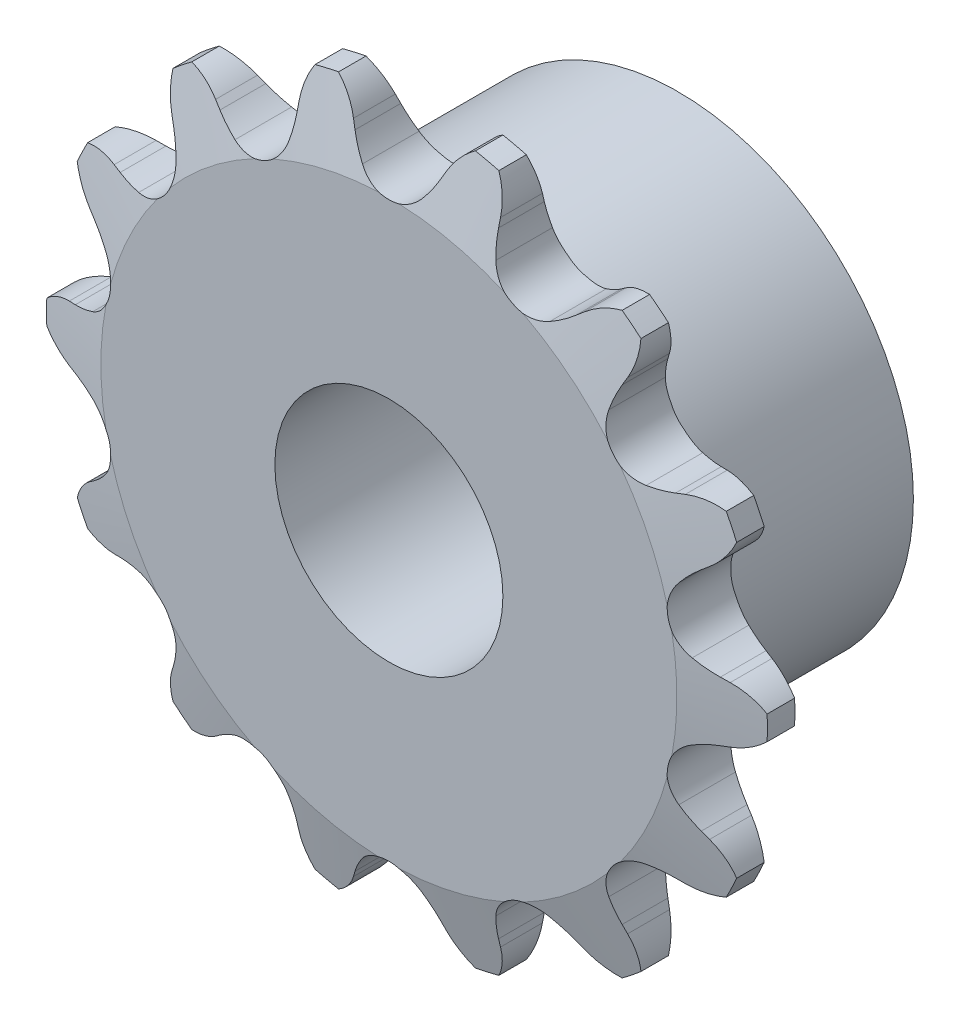
SolidWorks part; units mm, degrees
ref_plane "Front Plane" through (0, 0, 0) normal (0, 0, 1) x (1, 0, 0)
ref_plane "Top Plane" through (0, 0, 0) normal (0, 1, 0) x (1, 0, 0)
ref_plane "Right Plane" through (0, 0, 0) normal (1, 0, 0) x (0, 0, -1)
ref_axis "Axis1" through (0, 0, -88.99) along (0, 0, 1)
sketch "Sprocket-BaseSketch" plane through (0, 0, 0) normal (1, 0, 0) x (0, 0, -1)
  line L0 (1.397, 0) -> (1.397, 12.6406)
  line L1 (1.397, 12.6406) -> (0.6032, 15.8156)
  line L2 (0.6032, 15.8156) -> (-0.6032, 15.8156)
  line L3 (-0.6032, 15.8156) -> (-1.397, 12.6406)
  line L4 (-1.397, 12.6406) -> (-1.397, 0)
  line L5 (-1.397, 0) -> (1.397, 0)
  line L6 (5.588, 0) -> (-1.7463, 0) construction
  dimension "Hub Surface" = 1.397
  dimension "RightSide (1)" = 0.7938
  dimension "RightSide (2)" = 3.175
  dimension "OD" = 15.8156
  dimension "LeftSide (1)" = 0.7938
  dimension "LeftSide (2)" = 3.175
  dimension "Tooth Width" = 2.794
revolve "25 (04C) ANSI (ISO) Chain Number, 1.123in P.D." add sketch "Sprocket-BaseSketch" angle 360 about L6
sketch "Tooth-Sketch" plane through (0, 0, 0) normal (0, 0, 1) x (1, 0, 0)
  line L0 (0, 0) -> (0, 19.0244) construction
  line L1 (1.8786, 14.0876) -> (2.0306, 14.4094)
  line L2 (-1.8786, 14.0876) -> (-2.0306, 14.4094)
  line L3 (0, 14.2683) -> (6.1908, 12.8553) construction
  line L4 (0, 14.2683) -> (-6.1908, 12.8553) construction
  arc A0 (-1.3137, 13.1936) -> (1.3137, 13.1936) centre (0, 14.2683) ccw
  arc A1 (1.3137, 13.1936) -> (1.8786, 14.0876) centre (-2.0446, 15.9409) ccw
  arc A2 (-1.3137, 13.1936) -> (-1.8786, 14.0876) centre (2.0446, 15.9409) cw
  arc A3 (2.0306, 14.4094) -> (4.5069, 15.9783) centre (4.5069, 13.2397) cw
  arc A4 (-2.0306, 14.4094) -> (-4.5069, 15.9783) centre (-4.5069, 13.2397) ccw
  arc A5 (4.5069, 15.9783) -> (-4.5069, 15.9783) centre (0, 0) ccw
extrude "Tooth-Cut, Number of teeth: 14" cut sketch "Tooth-Sketch" against normal through all and the other way through all
pattern_circular "Tooth Pattern, 14 / 14" count 14 every 25.714 about axis through (0, 0, -88.99) along (0, 0, 1) of "Tooth-Cut, Number of teeth: 14"
sketch "Sketch3" plane through (0, 0, 0) normal (1, 0, 0) x (0, 0, -1)
  line L0 (-9.906, 0) -> (9.906, 0) construction
  line L1 (1.397, 0) -> (1.397, 10.3187)
  line L2 (1.397, 10.3187) -> (11.303, 10.3187)
  line L3 (11.303, 10.3187) -> (11.303, 0)
  line L4 (11.303, 0) -> (1.397, 0)
  dimension "Hub Mounting" = 1.397
  dimension "Hub OD" = 10.3187
  dimension "Hub Width" = 9.906
revolve "Hub-Revolve1" add sketch "Sketch3" angle 360 about L0
sketch "Sketch4" plane through (0, 0, 0) normal (0, 0, 1) x (1, 0, 0)
  circle A0 centre (0, 0) radius 5.0038
  dimension "D1" = 10.0076
extrude "Cut-Extrude1" cut sketch "Sketch4" against normal through all and the other way through all
sketch "Sketch5" plane through (0, 0, 0) normal (0, 0, 1) x (1, 0, 0)
  circle A0 centre (0, 0) radius 15.8156
  dimension "D1" = 31.6312
equation "\"D1@Sketch5\" = \"OD@Sprocket-BaseSketch\"*2"
